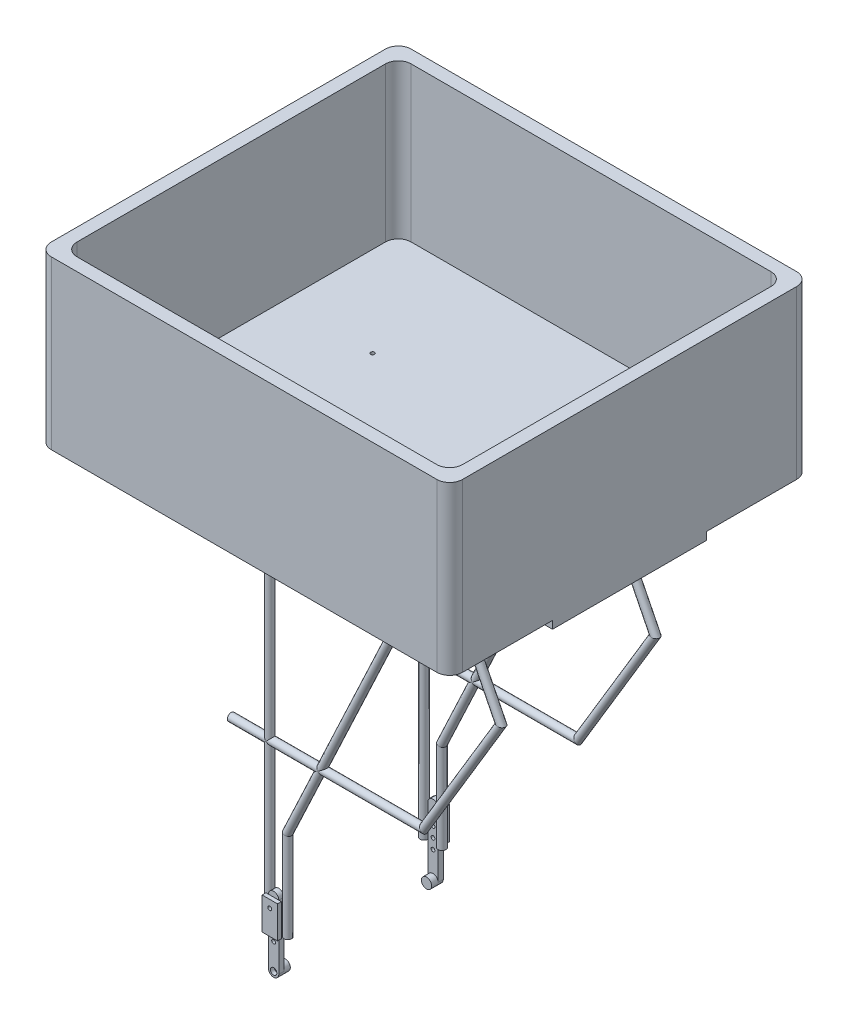
SolidWorks part; units mm, degrees
ref_plane "Front Plane" through (0, 0, 0) normal (0, 0, 1) x (1, 0, 0)
ref_plane "Top Plane" through (0, 0, 0) normal (0, 1, 0) x (1, 0, 0)
ref_plane "Right Plane" through (0, 0, 0) normal (1, 0, 0) x (0, 0, -1)
sketch "Sketch1" plane through (0, 0, 0) normal (0, 1, 0) x (1, 0, 0)
  line L1 (0, 0) -> (406.4, 0)
  line L2 (0, 0) -> (0, -355.6)
  line L3 (0, -355.6) -> (406.4, -355.6)
  line L4 (406.4, 0) -> (406.4, -355.6)
  dimension "D1" = 406.4
  dimension "D2" = 355.6
extrude "Boss-Extrude1" add sketch "Sketch1" along normal blind 165.1
fillet "Fillet1" radius 12.7 1 edges at (0, 82.55, 0) type face fillet first side face at (203.2, 82.55, 0) second side face at (0, 82.55, 177.8)
fillet "Fillet2" radius 12.7 1 edges at (0, 82.55, 355.6) type face fillet first side face at (203.2, 82.55, 355.6) second side face at (0, 82.55, 184.15)
fillet "Fillet3" radius 12.7 1 edges at (406.4, 82.55, 0) type face fillet first side face at (209.55, 82.55, 0) second side face at (406.4, 82.55, 177.8)
fillet "Fillet4" radius 12.7 1 edges at (406.4, 82.55, 355.6) type face fillet first side face at (406.4, 82.55, 184.15) second side face at (209.55, 82.55, 355.6)
shell "Shell1" thickness 12.7 removed face at (203.2, 165.1, 177.8)
fillet "Fillet5" radius 12.7 1 edges at (12.7, 88.9, 12.7) type face fillet first side face at (203.2, 88.9, 12.7) second side face at (12.7, 88.9, 177.8)
fillet "Fillet6" radius 12.7 1 edges at (12.7, 88.9, 342.9) type face fillet first side face at (12.7, 88.9, 184.15) second side face at (203.2, 88.9, 342.9)
fillet "Fillet7" radius 12.7 1 edges at (393.7, 88.9, 12.7) type face fillet first side face at (209.55, 88.9, 12.7) second side face at (393.7, 88.9, 177.8)
fillet "Fillet8" radius 12.7 1 edges at (393.7, 88.9, 342.9) type face fillet first side face at (209.55, 88.9, 342.9) second side face at (393.7, 88.9, 184.15)
sketch "Sketch2" plane through (0, 0, 0) normal (0, -1, 0) x (1, 0, 0)
  line L0 (0, 12.7) -> (0, 342.9) construction
  line L1 (0, 254) -> (406.4, 254)
  line L2 (0, 254) -> (0, 101.6)
  line L3 (0, 101.6) -> (406.4, 101.6)
  line L4 (406.4, 254) -> (406.4, 101.6)
  line L5 (406.4, 342.9) -> (406.4, 12.7) construction
  line L6 (12.7, 355.6) -> (393.7, 355.6) construction
  dimension "D1" = 152.4
  dimension "D2" = 101.6
extrude "Boss-Extrude2" add sketch "Sketch2" along normal blind 7.62
sketch "Sketch3" plane through (0, 0, 254) normal (0, 0, 1) x (1, 0, 0)
  line L0 (25.4, -3.81) -> (-136.8827, -126.0988) construction
  line L1 (27.6929, -6.8528) -> (-134.5898, -129.1416)
  line L2 (23.1071, -0.7672) -> (-139.1757, -123.056)
  line L3 (0, -7.62) -> (0, 0) construction
  line L4 (406.4, -7.62) -> (0, -7.62) construction
  line L5 (406.4, 0) -> (0, 0) construction
  arc A0 (27.6929, -6.8528) -> (23.1071, -0.7672) centre (25.4, -3.81) ccw
  arc A1 (-139.1757, -123.056) -> (-134.5898, -129.1416) centre (-136.8827, -126.0988) ccw
  point P2 (-55.7414, -64.9544)
  dimension "D1" = 3.81
  dimension "D2" = 203.2
  dimension "D3" = 25.4
  dimension "D4" = 37
  dimension "D5" = 3.81
extrude "Boss-Extrude3" add sketch "Sketch3" along normal blind 3.81 from offset 60.96 offset against normal yes
sketch "Sketch4" plane through (0, 0, 101.6) normal (0, 0, -1) x (-1, 0, 0)
  line L0 (136.8827, -126.0988) -> (-25.4, -3.81) construction
  line L1 (134.5898, -129.1416) -> (-27.6929, -6.8528)
  line L2 (139.1757, -123.056) -> (-23.1071, -0.7672)
  line L3 (0, -7.62) -> (0, 0) construction
  arc A0 (134.5898, -129.1416) -> (139.1757, -123.056) centre (136.8827, -126.0988) ccw
  arc A1 (-23.1071, -0.7672) -> (-27.6929, -6.8528) centre (-25.4, -3.81) ccw
  point P3 (55.7414, -64.9544)
  dimension "D3" = 3.81
  dimension "D1" = 203.2
  dimension "D2" = 25.4
extrude "Boss-Extrude4" add sketch "Sketch4" along normal blind 3.81 from offset 60.96 offset against normal yes
sketch "Sketch5" plane through (0, 0, 254) normal (0, 0, 1) x (1, 0, 0)
  line L0 (127, 0) -> (127, -401.32)
  line L2 (406.4, -7.62) -> (0, -7.62) construction
  line L5 (406.4, 0) -> (0, 0) construction
  dimension "D1" = 127
  dimension "D3" = 0
  dimension "D6" = 393.7
sweep "Sweep1" add path "Sketch5" circular profile diameter 7.62 parameters "D3"=7.62
sketch "Sketch15" plane through (0, 0, 254) normal (0, 0, 1) x (1, 0, 0)
  line L0 (279.4, 0) -> (279.4, -25.4)
  line L1 (406.4, 0) -> (130.81, 0) construction
  line L2 (279.4, -25.4) -> (144.78, -312.42)
  line L3 (144.78, -312.42) -> (144.78, -401.32)
  line L4 (406.4, -7.62) -> (130.81, -7.62) construction
  line L6 (406.4, -7.62) -> (406.4, 0) construction
  line L7 (130.81, -401.32) -> (130.81, -7.62) construction
  dimension "D1" = 393.7
  dimension "D2" = 25.4
  dimension "D3" = 88.9
  dimension "D4" = 127
  dimension "D5" = 13.97
sweep "Sweep2" add path "Sketch15" circular profile diameter 7.62 parameters "D3"=7.62
sketch "Sketch24" plane through (0, 0, 101.6) normal (0, 0, -1) x (-1, 0, 0)
  line L0 (-127, 0) -> (-127, -401.32)
  line L1 (0, 0) -> (-406.4, 0) construction
  line L2 (-130.81, -401.32) -> (-123.19, -401.32) construction
  dimension "D1" = 127
sweep "Sweep3" add path "Sketch24" circular profile diameter 7.62 parameters "D3"=7.62
sketch "Sketch33" plane through (0, 0, 101.6) normal (0, 0, -1) x (-1, 0, 0)
  line L0 (-279.4, 0) -> (-279.4, -25.4)
  line L1 (-393.7, 0) -> (-12.7, 0) construction
  line L2 (-283.21, -26.2491) -> (-275.59, -24.5509) construction
  line L3 (-279.4, -25.4) -> (-144.78, -312.42)
  line L4 (-144.78, -312.42) -> (-144.78, -401.32)
  line L5 (-148.59, -401.32) -> (-140.97, -401.32) construction
  dimension "D1" = 88.9
sweep "Sweep4" add path "Sketch33" circular profile diameter 7.62 parameters "D3"=7.62
sketch "Sketch42" plane through (0, 0, 101.6) normal (0, 0, -1) x (-1, 0, 0)
  line L0 (-88.9, -38.1) -> (-317.5, -38.1)
  line L1 (-317.5, -38.1) -> (-355.6, -114.3)
  line L2 (-355.6, -114.3) -> (-279.4, -241.3)
  line L3 (-279.4, -241.3) -> (-88.9, -241.3)
  line L4 (-130.81, 0) -> (-275.59, 0) construction
  dimension "D1" = 38.1
  dimension "D2" = 228.6
  dimension "D3" = 203.2
  dimension "D4" = 127
  dimension "D5" = 88.9
  dimension "D6" = 88.9
  dimension "D7" = 76.2
  dimension "D8" = 279.4
sweep "Sweep5" add path "Sketch42" circular profile diameter 7.62 parameters "D3"=7.62
sketch "Sketch51" plane through (0, 0, 254) normal (0, 0, 1) x (1, 0, 0)
  line L0 (88.9, -38.1) -> (317.5, -38.1)
  line L1 (88.9, -34.29) -> (88.9, -41.91) construction
  line L2 (319.8547, -34.29) -> (315.1453, -41.91) construction
  line L3 (317.5, -38.1) -> (355.6, -114.3)
  line L4 (359.9431, -114.4668) -> (351.2569, -114.1332) construction
  line L5 (355.6, -114.3) -> (279.4, -241.3)
  line L6 (281.5572, -245.11) -> (277.2428, -237.49) construction
  line L7 (279.4, -241.3) -> (88.9, -241.3)
  line L8 (88.9, -237.49) -> (88.9, -245.11) construction
sweep "Sweep6" add path "Sketch51" circular profile diameter 7.62 parameters "D3"=7.62
sketch "Sketch60" plane through (0, 0, 254) normal (0, 0, 1) x (1, 0, 0)
  line L0 (135.89, -369.57) -> (135.89, -433.07) construction
  line L1 (140.97, -369.57) -> (140.97, -433.07)
  line L2 (130.81, -369.57) -> (130.81, -433.07)
  line L3 (12.7, 0) -> (393.7, 0) construction
  line L4 (123.19, -245.11) -> (123.19, -401.32) construction
  arc A0 (140.97, -369.57) -> (130.81, -369.57) centre (135.89, -369.57) ccw
  arc A1 (130.81, -433.07) -> (140.97, -433.07) centre (135.89, -433.07) ccw
  point P2 (135.89, -401.32)
  dimension "D1" = 5.08
  dimension "D2" = 63.5
  dimension "D3" = 12.7
  dimension "D4" = 369.57
extrude "Boss-Extrude5" add sketch "Sketch60" along normal blind 5.08 separate body
sketch "Sketch62" plane through (0, 0, 101.6) normal (0, 0, -1) x (-1, 0, 0)
  line L0 (-135.89, -369.57) -> (-135.89, -433.07) construction
  line L1 (-130.81, -369.57) -> (-130.81, -433.07)
  line L2 (-140.97, -369.57) -> (-140.97, -433.07)
  arc A0 (-130.81, -369.57) -> (-140.97, -369.57) centre (-135.89, -369.57) ccw
  arc A1 (-140.97, -433.07) -> (-130.81, -433.07) centre (-135.89, -433.07) ccw
  point P4 (-135.89, -401.32)
  dimension "D1" = 5.08
extrude "Boss-Extrude6" add sketch "Sketch62" along normal blind 5.08 separate body
sketch "Sketch64" plane through (0, 0, 96.52) normal (0, 0, -1) x (-1, 0, 0)
  line L5 (-130.81, -401.32) -> (-123.19, -401.32) construction
  line L6 (-143.51, -369.57) -> (-128.27, -369.57)
  line L7 (-143.51, -369.57) -> (-143.51, -401.32)
  line L8 (-143.51, -401.32) -> (-128.27, -401.32)
  line L9 (-128.27, -369.57) -> (-128.27, -401.32)
  line L10 (-140.97, -369.57) -> (-140.97, -433.07) construction
  line L11 (-130.81, -433.07) -> (-130.81, -369.57) construction
  dimension "D1" = 2.54
  dimension "D2" = 2.54
  dimension "D3" = 31.75
sketch "Sketch65" plane through (0, 0, 259.08) normal (0, 0, 1) x (1, 0, 0)
  line L6 (140.97, -433.07) -> (140.97, -369.57) construction
  line L7 (128.27, -369.57) -> (143.51, -369.57)
  line L8 (128.27, -369.57) -> (128.27, -401.32)
  line L9 (128.27, -401.32) -> (143.51, -401.32)
  line L10 (143.51, -369.57) -> (143.51, -401.32)
  line L11 (130.81, -369.57) -> (130.81, -433.07) construction
  line L12 (12.7, 0) -> (393.7, 0) construction
  dimension "D1" = 2.54
  dimension "D2" = 31.75
  dimension "D3" = 2.54
  dimension "D4" = 401.32
sketch "Sketch67" plane through (0, 0, 254) normal (0, 0, -1) x (-1, 0, 0)
  circle A0 centre (-135.89, -433.07) radius 5.08
  dimension "D1" = 10.16
extrude "Boss-Extrude9" add sketch "Sketch67" along normal blind 6.35
sketch "Sketch68" plane through (0, 0, 101.6) normal (0, 0, 1) x (1, 0, 0)
  circle A0 centre (135.89, -433.07) radius 5.08
  arc A1 (130.81, -433.07) -> (140.97, -433.07) centre (135.89, -433.07) ccw construction
  dimension "D1" = 10.16
  dimension "D2" = 0
extrude "Boss-Extrude10" add sketch "Sketch68" along normal blind 6.35
sketch "Sketch69" plane through (0, 0, 259.08) normal (0, 0, 1) x (1, 0, 0)
  circle A0 centre (135.89, -433.07) radius 3.175
  dimension "D1" = 6.35
extrude "Cut-Extrude1" cut sketch "Sketch69" against normal blind 3.81
sketch "Sketch70" plane through (0, 0, 96.52) normal (0, 0, -1) x (-1, 0, 0)
  circle A0 centre (-135.89, -433.07) radius 3.175
  dimension "D1" = 6.35
extrude "Cut-Extrude2" cut sketch "Sketch70" against normal blind 3.81
sketch "Sketch71" plane through (0, 0, 96.52) normal (0, 0, -1) x (-1, 0, 0)
  line L0 (-130.81, -433.07) -> (-130.81, -369.57) construction
  circle A0 centre (-135.89, -407.67) radius 1.905
  circle A1 centre (-135.89, -387.35) radius 1.905
  circle A2 centre (-135.89, -397.51) radius 1.905
  circle A3 centre (-135.89, -377.19) radius 1.905
  circle A5 centre (-135.89, -433.07) radius 3.175 construction
  circle A6 centre (-135.89, -433.07) radius 3.175 construction
  dimension "D1" = 3.81
  dimension "D2" = 3.81
  dimension "D3" = 3.81
  dimension "D4" = 3.81
  dimension "D12" = 55.88
  dimension "D5" = 25.4
  dimension "D6" = 10.16
  dimension "D7" = 10.16
  dimension "D8" = 10.16
  dimension "D9" = 5.08
  dimension "D10" = 35.56
  dimension "D11" = 45.72
extrude "Cut-Extrude3" cut sketch "Sketch71" against normal through all
extrude "Boss-Extrude11" add sketch "Sketch64" along normal blind 3.81
extrude "Boss-Extrude12" add sketch "Sketch65" along normal blind 3.81
sketch "Sketch72" plane through (0, 0, 259.08) normal (0, 0, -1) x (-1, 0, 0)
  circle A0 centre (-135.89, -377.19) radius 1.905
  dimension "D1" = 3.81
extrude "Cut-Extrude4" cut sketch "Sketch72" along normal through all from offset 33.02 offset against normal yes
sketch "Sketch73" plane through (0, 0, 196.85) normal (0, 0, 1) x (1, 0, 0)
  circle A0 centre (-136.8827, -126.0988) radius 1.905
  dimension "D1" = 3.81
extrude "Cut-Extrude5" cut sketch "Sketch73" against normal through all
sketch "Sketch74" plane through (0, 0, 254) normal (0, 0, 1) x (1, 0, 0)
  line L0 (283.21, -7.62) -> (283.21, 0) construction
  line L1 (275.59, 0) -> (275.59, -7.62) construction
  line L4 (275.59, 0) -> (283.21, 0) construction
  line L5 (12.7, 0) -> (393.7, 0) construction
  line L6 (123.19, -7.62) -> (123.19, 0) construction
  circle A0 centre (127, -3.81) radius 1.905
  circle A1 centre (279.4, -3.8466) radius 1.905
  dimension "D1" = 3.81
  dimension "D2" = 3.81
  dimension "D4" = 3.81
  dimension "D5" = 3.8466
  dimension "D7" = 3.81
  dimension "D3" = 7.62
  dimension "D6" = 3.81
extrude "Cut-Extrude6" cut sketch "Sketch74" against normal blind 3.81 from offset 5.08
sketch "Sketch75" plane through (0, 0, 101.6) normal (0, 0, -1) x (-1, 0, 0)
  line L0 (-275.59, -7.62) -> (-275.59, 0) construction
  line L1 (-393.7, 0) -> (-12.7, 0) construction
  line L2 (-123.19, 0) -> (-123.19, -7.62) construction
  line L3 (-130.81, 0) -> (-123.19, 0) construction
  circle A0 centre (-127, -3.81) radius 1.905
  circle A1 centre (-279.4, -3.81) radius 1.905
  dimension "D1" = 3.81
  dimension "D2" = 3.81
  dimension "D3" = 3.81
  dimension "D4" = 3.81
  dimension "D5" = 3.81
  dimension "D6" = 3.81
extrude "Cut-Extrude7" cut sketch "Sketch75" against normal blind 3.81 from offset 5.08
sketch "Sketch76" plane through (0, -7.62, 0) normal (0, -1, 0) x (1, 0, 0)
  line L0 (0, 177.8) -> (406.4, 177.8) construction
  line L1 (0, 254) -> (0, 101.6) construction
  line L2 (406.4, 101.6) -> (406.4, 254) construction
  line L3 (203.2, 355.6) -> (203.2, 0) construction
  line L4 (12.7, 355.6) -> (393.7, 355.6) construction
  line L5 (393.7, 0) -> (12.7, 0) construction
  circle A0 centre (101.6, 228.6) radius 1.905
  circle A1 centre (101.6, 127) radius 1.905
  circle A2 centre (304.8, 228.6) radius 1.905
  circle A3 centre (304.8, 127) radius 1.905
  dimension "D1" = 3.81
  dimension "D2" = 101.6
  dimension "D3" = 127
extrude "Cut-Extrude8" cut sketch "Sketch76" against normal through all
